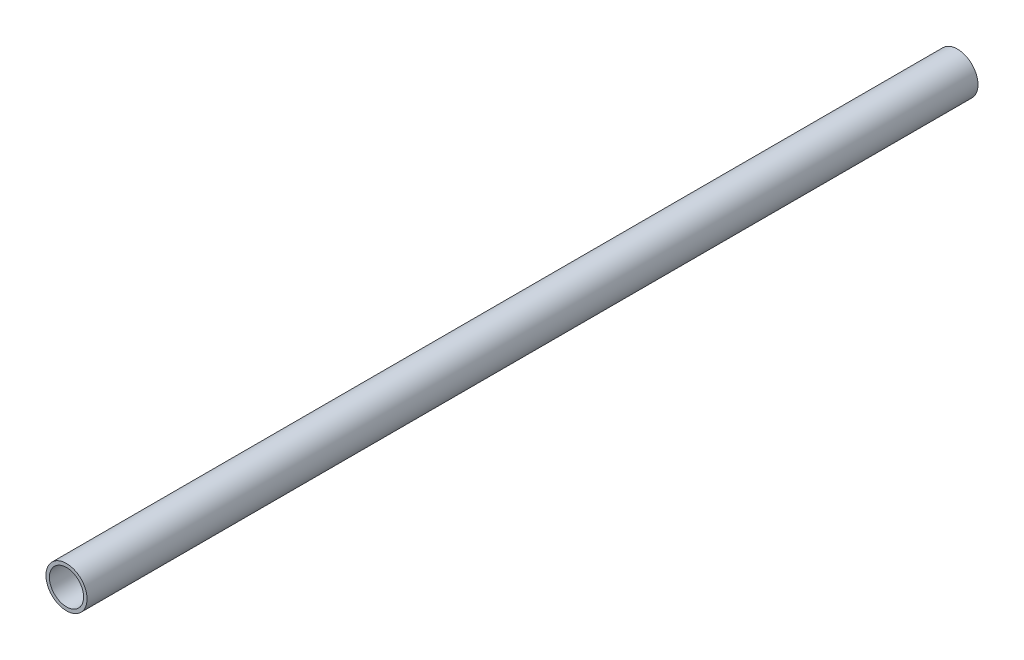
SolidWorks part; units mm, degrees
ref_plane "Front Plane" through (0, 0, 0) normal (0, 0, 1) x (1, 0, 0)
ref_plane "Top Plane" through (0, 0, 0) normal (0, 1, 0) x (1, 0, 0)
ref_plane "Right Plane" through (0, 0, 0) normal (1, 0, 0) x (0, 0, -1)
sketch "Sketch1" plane through (0, 0, 0) normal (0, 0, 1) x (1, 0, 0)
  circle A0 centre (0, 0) radius 21.082
  dimension "Pipe OD" = 42.164
extrude "Extrude-Thin1" add sketch "Sketch1" along normal mid plane 914.4 thin thin type one direction reverse wall 3.556
